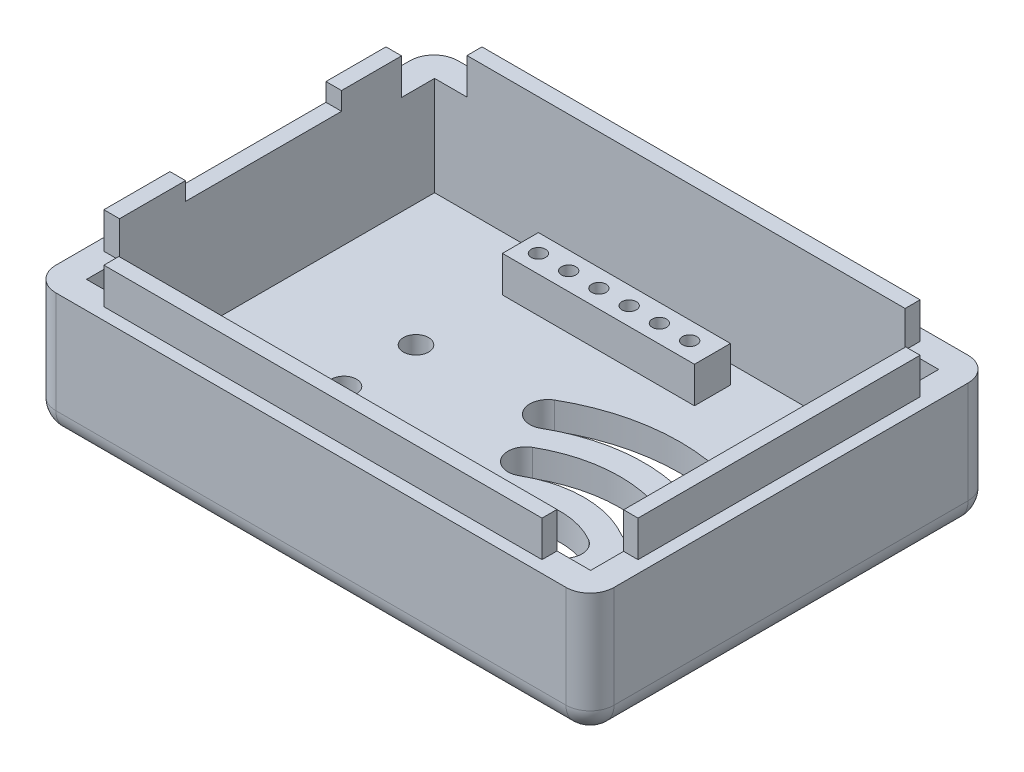
SolidWorks part; units mm, degrees
ref_plane "Front Plane" through (0, 0, 0) normal (0, 0, 1) x (1, 0, 0)
ref_plane "Top Plane" through (0, 0, 0) normal (0, 1, 0) x (1, 0, 0)
ref_plane "Right Plane" through (0, 0, 0) normal (1, 0, 0) x (0, 0, -1)
sketch "Sketch1" plane through (0, 0, 0) normal (0, 1, 0) x (1, 0, 0)
  line L5 (0, 0) -> (-46.5, 0)
  line L6 (0, 0) -> (0, 33.5)
  line L7 (0, 33.5) -> (-46.5, 33.5)
  line L8 (-46.5, 0) -> (-46.5, 33.5)
  dimension "D1" = 33.5
  dimension "D2" = 46.5
extrude "Boss-Extrude1" add sketch "Sketch1" along normal blind 13.5
sketch "Sketch2" plane through (0, 13.5, 0) normal (0, 1, 0) x (1, 0, 0)
  line L1 (-44.2, 31.25) -> (-2.2, 31.25)
  line L2 (-44.2, 31.25) -> (-44.2, 2.25)
  line L3 (-44.2, 2.25) -> (-2.2, 2.25)
  line L4 (-2.2, 31.25) -> (-2.2, 2.25)
  dimension "D1" = 42
  dimension "D2" = 2.2
  dimension "D3" = 2.25
  dimension "D4" = 29
extrude "Cut-Extrude1" cut sketch "Sketch2" against normal blind 11.25
fillet "Fillet1" radius 2 8 edges at (-46.5, 6.75, 0) (-46.5, 6.75, -33.5) (0, 6.75, -33.5) (0, 6.75, 0) (-46.5, 0, -16.75) (-23.25, 0, -33.5) (0, 0, -16.75) (-23.25, 0, 0)
sketch "Sketch3" plane through (0, 2.25, 0) normal (0, 1, 0) x (1, 0, 0)
  circle A0 centre (-34, 16.5) radius 2.5
  dimension "D2" = 5
  dimension "D1" = 16.5
  dimension "D3" = 34
sketch "Sketch4" plane through (0, 2.25, 0) normal (0, 1, 0) x (1, 0, 0)
  circle A0 centre (-34, 19.5) radius 1.05
  circle A2 centre (-34, 13.5) radius 1.05
  dimension "D2" = 2.1
  dimension "D5" = 2.1
  dimension "D1" = 19.5
  dimension "D3" = 34
  dimension "D4" = 34
  dimension "D6" = 13.5
extrude "Cut-Extrude2" cut sketch "Sketch4" against normal blind 11.25
sketch "Sketch5" plane through (0, 2.25, 0) normal (0, 1, 0) x (1, 0, 0)
  line L1 (-41, 8) -> (-34, 8)
  line L2 (-41, 8) -> (-41, 3.5)
  line L3 (-41, 3.5) -> (-34, 3.5)
  line L4 (-34, 8) -> (-34, 3.5)
  dimension "D1" = 34
  dimension "D2" = 7
  dimension "D3" = 4.5
  dimension "D4" = 3.5
extrude "Cut-Extrude3" cut sketch "Sketch5" against normal blind 11.25
sketch "Sketch6" plane through (0, 2.25, 0) normal (0, 1, 0) x (1, 0, 0)
  line L0 (-16, 7) -> (-28.3417, 28.3765)
  line L1 (0, -7.425) -> (0, 7.425) construction
  line L2 (-16, 7) -> (-3.5595, 28.5475)
  circle A0 centre (-16, 7) radius 1.5
  arc A4 (-18.5, 11.3301) -> (-13.5, 11.3301) centre (-16, 7) cw
  arc A5 (-21, 15.6603) -> (-11, 15.6603) centre (-16, 7) cw
  arc A6 (-23.5, 19.9904) -> (-8.5, 19.9904) centre (-16, 7) cw
  circle A7 centre (-23.5, 19.9904) radius 1.5
  circle A8 centre (-21, 15.6603) radius 1.5
  circle A9 centre (-11, 15.6603) radius 1.5
  circle A10 centre (-18.5, 11.3301) radius 1.5
  circle A11 centre (-13.5, 11.3301) radius 1.5
  circle A12 centre (-8.5, 19.9904) radius 1.5
  arc A13 (-22.75, 18.6913) -> (-9.25, 18.6913) centre (-16, 7) cw
  arc A14 (-20.25, 14.3612) -> (-11.75, 14.3612) centre (-16, 7) cw
  arc A15 (-17.75, 10.0311) -> (-14.25, 10.0311) centre (-16, 7) cw
  arc A16 (-24.25, 21.2894) -> (-7.75, 21.2894) centre (-16, 7) cw
  arc A17 (-21.75, 16.9593) -> (-10.25, 16.9593) centre (-16, 7) cw
  arc A18 (-19.25, 12.6292) -> (-12.75, 12.6292) centre (-16, 7) cw
  dimension "D3" = 3
  dimension "D4" = 5
  dimension "D5" = 10
  dimension "D6" = 15
  dimension "D7" = 30
  dimension "D15" = 3
  dimension "D16" = 3
  dimension "D17" = 3
  dimension "D18" = 3
  dimension "D19" = 3
  dimension "D20" = 3
  dimension "D1" = 16
  dimension "D2" = 7
  dimension "D8" = 0
  dimension "D9" = 0
  dimension "D10" = 0
  dimension "D11" = 30
  dimension "D12" = 0
  dimension "D13" = 0
  dimension "D14" = 0
  dimension "D21" = 1.5
  dimension "D22" = 1.5
extrude "Cut-Extrude4" cut sketch "Sketch6" against normal blind 11.25 contours A16 A7 A6 A12 | A7 A13 A12 A6 | L0 A7 A6 | A6 A7 L0 | L2 A12 A6 | A6 A12 L2 | L2 A12 | L2 A9 | L2 A11 | L2 A11 A4 | A4 A11 L2 | A5 A9 L2 | L2 A9 A5 | A17 A8 A5 A9 | A8 A14 A9 A5 | L0 A8 A5 | A5 A8 L0 | L0 A8 | L0 A7 | L0 A10 | A4 A10 L0 | L0 A10 A4 | A18 A10 A4 A11 | A10 A15 A11 A4 | L0 A0 L2 | L2 A0 L0 region at (-19.0513, 2.25, -11.0118) region at (-17.6396, 2.25, -11.047) region at (-16, 2.25, -11.1533) region at (-18.2206, 2.25, -12.1778) region at (-16, 2.25, -7.9549) region at (-16, 2.25, -6.809) region at (-16, 2.25, -12.7675) region at (-14.3604, 2.25, -11.047) region at (-12.9487, 2.25, -11.0118) region at (-21.5513, 2.25, -15.3419) region at (-20.1343, 2.25, -15.402) region at (-16, 2.25, -15.9912) region at (-13.7794, 2.25, -12.1778) region at (-20.7436, 2.25, -16.5195) region at (-16, 2.25, -17.4922) region at (-11.8657, 2.25, -15.402) region at (-10.4487, 2.25, -15.3419) region at (-24.0513, 2.25, -19.6721) region at (-22.6329, 2.25, -19.7405) region at (-16, 2.25, -20.7811) region at (-11.2564, 2.25, -16.5195) region at (-23.2513, 2.25, -20.8532) region at (-16, 2.25, -22.2562) region at (-9.3671, 2.25, -19.7405) region at (-7.9487, 2.25, -19.6721) region at (-8.7487, 2.25, -20.8532)
sketch "Sketch7" plane through (0, 2.25, 0) normal (0, 1, 0) x (1, 0, 0)
  line L0 (-46.5, 31.5) -> (-46.5, 2) construction
  circle A0 centre (-40.25, 8) radius 1
  dimension "D2" = 2
  dimension "D1" = 6.25
  dimension "D3" = 8
extrude "Cut-Extrude5" cut sketch "Sketch7" against normal blind 11.25
ref_plane "Plane1" through (0, 0, -16.75) normal (0, 0, 1) x (1, 0, 0)
sketch "Sketch8" plane through (0, 2.25, 0) normal (0, 1, 0) x (1, 0, 0)
  line L1 (-34, 6.8) -> (-18, 6.8)
  line L2 (-34, 6.8) -> (-34, 3.8)
  line L3 (-34, 3.8) -> (-18, 3.8)
  line L4 (-18, 6.8) -> (-18, 3.8)
  dimension "D1" = 18
  dimension "D2" = 3
  dimension "D3" = 3.8
  dimension "D4" = 16
extrude "Boss-Extrude2" add sketch "Sketch8" along normal blind 3
sketch "Sketch9" plane through (0, 5.25, 0) normal (0, 1, 0) x (1, 0, 0)
  circle A0 centre (-32.5, 5.3) radius 0.6
  point P0 (-32.5, 5.3)
  dimension "D3" = 1.2
  dimension "D1" = 32.5
  dimension "D2" = 5.3
extrude "Cut-Extrude6" cut sketch "Sketch9" against normal blind 3
pattern_linear "LPattern1" count 6 spacing 2.52 along (1, 0, 0) of "Cut-Extrude6"
mirror "Mirror1" about plane through (0, 0, -16.75) normal (0, 0, 1) of "LPattern1", "Cut-Extrude6", "Boss-Extrude2"
ref_axis "Axis1" through (-32.5, 2.25, -5.3) along (0, 1, 0)
ref_axis "Axis2" through (-32.5, 2.25, -28.2) along (0, 1, 0)
ref_axis "Axis3" through (-19.9, 2.25, -5.3) along (0, 1, 0)
sketch "Sketch11" plane through (0, 13.5, 0) normal (0, 1, 0) x (1, 0, 0)
  line L0 (-47.5, 34.5) -> (1, 34.5)
  line L1 (-45.5, 32.5) -> (-1, 32.5)
  line L2 (-45.5, 32.5) -> (-45.5, 1)
  line L3 (-45.5, 1) -> (-1, 1)
  line L4 (-1, 32.5) -> (-1, 1)
  line L5 (1, 34.5) -> (1, -1)
  line L6 (-47.5, -1) -> (1, -1)
  line L7 (-47.5, 34.5) -> (-47.5, -1)
  dimension "D1" = 1
  dimension "D2" = 1
  dimension "D3" = 31.5
  dimension "D4" = 44.5
  dimension "D5" = 2
extrude "Cut-Extrude7" cut sketch "Sketch11" against normal blind 3
sketch "Sketch12" plane through (0, 13.5, 0) normal (0, 1, 0) x (1, 0, 0)
  line L1 (-47, 23.5) -> (-43, 23.5)
  line L2 (-47, 23.5) -> (-47, 10.5)
  line L3 (-47, 10.5) -> (-43, 10.5)
  line L4 (-43, 23.5) -> (-43, 10.5)
  point P4 (-45, 10.5)
  dimension "D1" = 13
  dimension "D2" = 4
  dimension "D3" = 43
  dimension "D4" = 10.5
extrude "Cut-Extrude8" cut sketch "Sketch12" against normal blind 1.5
sketch "Sketch13" plane through (0, 13.5, 0) normal (0, 1, 0) x (1, 0, 0)
  line L17 (-5, 5) -> (5, 5)
  line L18 (-5, 5) -> (-5, -5)
  line L19 (-5, -5) -> (5, -5)
  line L20 (5, 5) -> (5, -5)
  line L21 (-5, 5) -> (5, -5) construction
  line L22 (-5, -5) -> (5, 5) construction
  line L23 (-5, 28.5) -> (5, 28.5)
  line L24 (-5, 28.5) -> (-5, 38.5)
  line L25 (-5, 38.5) -> (5, 38.5)
  line L26 (5, 28.5) -> (5, 38.5)
  line L27 (-5, 28.5) -> (5, 38.5) construction
  line L28 (-5, 38.5) -> (5, 28.5) construction
  line L29 (-51.5, 28.5) -> (-41.5, 28.5)
  line L30 (-51.5, 28.5) -> (-51.5, 38.5)
  line L31 (-51.5, 38.5) -> (-41.5, 38.5)
  line L32 (-41.5, 28.5) -> (-41.5, 38.5)
  line L33 (-51.5, 28.5) -> (-41.5, 38.5) construction
  line L34 (-51.5, 38.5) -> (-41.5, 28.5) construction
  line L35 (-41.5, 5) -> (-51.5, 5)
  line L36 (-41.5, 5) -> (-41.5, -5)
  line L37 (-41.5, -5) -> (-51.5, -5)
  line L38 (-51.5, 5) -> (-51.5, -5)
  line L39 (-41.5, 5) -> (-51.5, -5) construction
  line L40 (-41.5, -5) -> (-51.5, 5) construction
  point P0 (0, 0)
  point P5 (0, 33.5)
  point P10 (-46.5, 33.5)
  point P15 (-46.5, 0)
  dimension "D1" = 10
  dimension "D2" = 10
  dimension "D3" = 10
  dimension "D4" = 10
  dimension "D5" = 0
  dimension "D6" = 33.5
  dimension "D7" = 33.5
  dimension "D8" = 46.5
  dimension "D9" = 46.5
  dimension "D10" = 10
  dimension "D11" = 10
  dimension "D12" = 10
  dimension "D13" = 10
extrude "Cut-Extrude9" cut sketch "Sketch13" against normal blind 3
fillet "Fillet2" radius 3 2 edges at (-41, 1.125, -7.3386) (-39.25, 1.125, -8)
